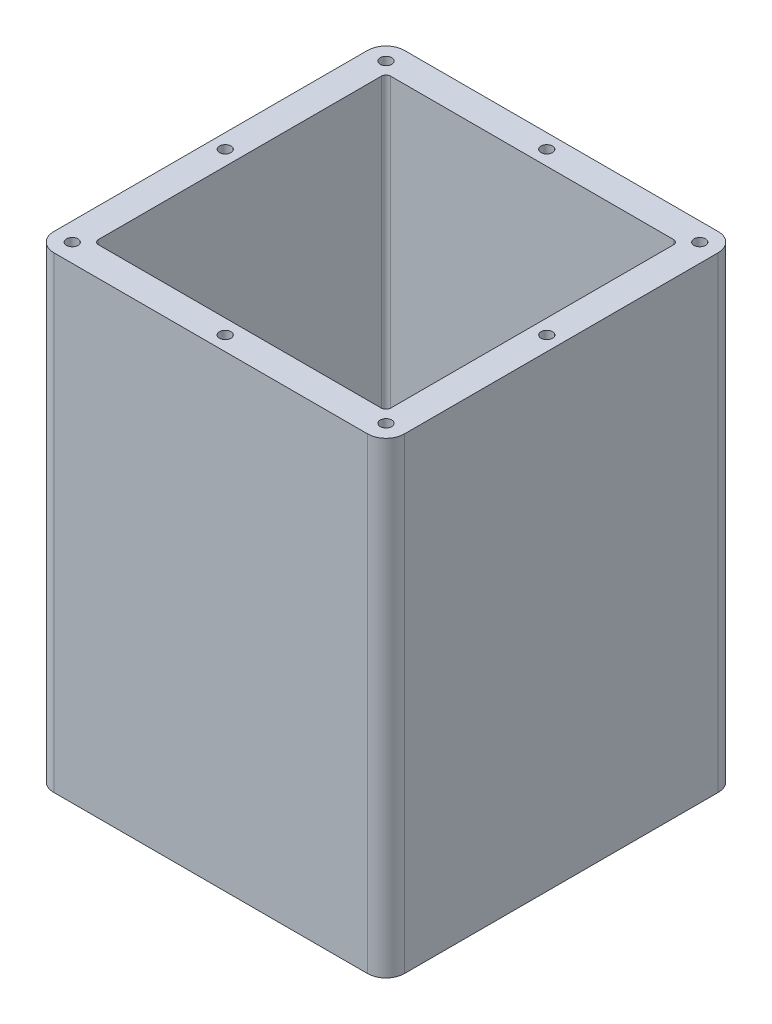
SolidWorks part; units mm, degrees
ref_plane "Front Plane" through (0, 0, 0) normal (0, 0, 1) x (1, 0, 0)
ref_plane "Top Plane" through (0, 0, 0) normal (0, 1, 0) x (1, 0, 0)
ref_plane "Right Plane" through (0, 0, 0) normal (1, 0, 0) x (0, 0, -1)
sketch "Sketch1" plane through (0, 0, 0) normal (0, 1, 0) x (1, 0, 0)
  line L1 (-35.56, -38.1) -> (35.56, -38.1)
  line L2 (-38.1, -35.56) -> (-38.1, 35.56)
  line L3 (-35.56, 38.1) -> (35.56, 38.1)
  line L4 (38.1, -35.56) -> (38.1, 35.56)
  line L5 (-38.1, -38.1) -> (38.1, 38.1) construction
  line L6 (-38.1, 38.1) -> (38.1, -38.1) construction
  arc A0 (-35.56, -38.1) -> (-38.1, -35.56) centre (-35.56, -35.56) cw
  arc A1 (35.56, -38.1) -> (38.1, -35.56) centre (35.56, -35.56) ccw
  arc A2 (35.56, 38.1) -> (38.1, 35.56) centre (35.56, 35.56) cw
  arc A3 (-38.1, 35.56) -> (-35.56, 38.1) centre (-35.56, 35.56) cw
  point P0 (0, 0)
  dimension "D3" = 2.54
  dimension "D1" = 76.2
  dimension "D2" = 76.2
extrude "Boss-Extrude1" add sketch "Sketch1" along normal blind 101.604
sketch "Sketch9" plane through (0, 101.604, 0) normal (0, 1, 0) x (1, 0, 0)
  line L0 (35.56, 38.1) -> (-35.56, 38.1) construction
  line L1 (-30.56, -33.1) -> (30.56, -33.1)
  line L2 (-33.1, -30.56) -> (-33.1, 30.56)
  line L3 (-30.56, 33.1) -> (30.56, 33.1)
  line L4 (33.1, -30.56) -> (33.1, 30.56)
  line L5 (-33.1, -33.1) -> (33.1, 33.1) construction
  line L6 (-33.1, 33.1) -> (33.1, -33.1) construction
  line L7 (38.1, -35.56) -> (38.1, 35.56) construction
  arc A0 (-30.56, -33.1) -> (-33.1, -30.56) centre (-30.56, -30.56) cw
  arc A1 (30.56, -33.1) -> (33.1, -30.56) centre (30.56, -30.56) ccw
  arc A2 (30.56, 33.1) -> (33.1, 30.56) centre (30.56, 30.56) cw
  arc A3 (-33.1, 30.56) -> (-30.56, 33.1) centre (-30.56, 30.56) cw
  point P0 (0, 0)
  dimension "D3" = 2.54
  dimension "D1" = 5
  dimension "D2" = 5
extrude "Cut-Extrude1" cut sketch "Sketch9" against normal blind 246.126
sketch "Sketch13" plane through (0, 0, -33.1) normal (0, 0, 1) x (1, 0, 0)
  line L1 (-20, 36.007) -> (20, 36.007)
  line L2 (-20, 36.007) -> (-20, 76.007)
  line L3 (-20, 76.007) -> (20, 76.007)
  line L4 (20, 36.007) -> (20, 76.007)
  line L5 (-20, 36.007) -> (20, 76.007) construction
  line L6 (-20, 76.007) -> (20, 36.007) construction
  point P0 (0, 56.007)
  dimension "D1" = 40
  dimension "D2" = 40
sketch "Sketch14" plane through (0, 101.604, 0) normal (0, 1, 0) x (1, 0, 0)
  line L2 (-38.1, -38.1) -> (38.1, -38.1)
  line L4 (-38.1, -38.1) -> (-38.1, 38.1)
  line L5 (-31.75, 31.75) -> (31.75, 31.75)
  line L6 (-31.75, 31.75) -> (-31.75, -31.75)
  line L7 (-31.75, -31.75) -> (31.75, -31.75)
  line L8 (31.75, 31.75) -> (31.75, -31.75)
  line L9 (-31.75, 31.75) -> (31.75, -31.75) construction
  line L10 (-31.75, -31.75) -> (31.75, 31.75) construction
  line L11 (-38.1, 38.1) -> (38.1, 38.1)
  line L12 (38.1, -38.1) -> (38.1, 38.1)
  line L13 (-38.1, -38.1) -> (38.1, 38.1) construction
  line L14 (-38.1, 38.1) -> (38.1, -38.1) construction
  point P0 (0, 0)
  point P9 (0, 0)
extrude "Boss-Extrude3" add sketch "Sketch14" against normal blind 101.604
fillet "Fillet1" radius 4 4 edges at (-38.1, 50.802, -38.1) (-38.1, 50.802, 38.1) (38.1, 50.802, 38.1) (38.1, 50.802, -38.1)
sketch "Sketch17" plane through (0, 101.604, 0) normal (0, 1, 0) x (1, 0, 0)
  point P0 (-34.1, 34.1)
  point P3 (34.1, 34.1)
  point P6 (34.1, -34.1)
  point P9 (-34.1, -34.1)
  point P21 (-34.95, 0)
  point P24 (34.95, 0)
  point P27 (0, -34.95)
  point P30 (0, 34.95)
hole_wizard "M3x0.5 Tapped Hole2" positions "Sketch17" profile "Sketch18" tap size "M3x0.5" standard "ANSI Metric"
sketch "Sketch18" plane through (-34.1, 101.604, -34.1) normal (1, 0, 0) x (0, 0, 1)
  line L0 (0, 0) -> (0, 8.2511)
  line L1 (0, 8.2511) -> (1.25, 7.5)
  line L2 (1.25, 7.5) -> (1.25, 0)
  line L5 (1.25, 0) -> (0, 0)
  line L10 (0, 8.2511) -> (-1.25, 7.5) construction
  line L11 (0, -6.35) -> (0, 107.95) construction
  dimension "Tap Drill Dia." = 2.5
  dimension "Tap Drill Depth" = 7.5
  dimension "Drill Angle" = 118
sketch "Sketch21" plane through (38.1, 0, 0) normal (1, 0, 0) x (0, 0, -1)
  circle A0 centre (0, 76.708) radius 10
  circle A1 centre (0, 33.7027) radius 10
  dimension "D2" = 20
  dimension "D3" = 20
sketch "Sketch24" plane through (0, 0, 0) normal (0, -1, 0) x (-1, 0, 0)
  point P0 (-34.1, 34.1)
  point P2 (34.1, 34.1)
  point P4 (34.1, -34.1)
  point P6 (-34.1, -34.1)
  point P16 (-34.95, 0)
  point P19 (0, 34.95)
  point P22 (34.95, 0)
  point P25 (0, -34.95)
hole_wizard "M3x0.5 Tapped Hole1" positions "Sketch24" profile "Sketch23" tap size "M3x0.5" standard "ANSI Metric"
sketch "Sketch23" plane through (34.1, 0, -34.1) normal (1, 0, 0) x (0, 0, -1)
  line L0 (0, 0) -> (0, 8.2511)
  line L1 (0, 8.2511) -> (1.25, 7.5)
  line L2 (1.25, 7.5) -> (1.25, 0)
  line L5 (1.25, 0) -> (0, 0)
  line L10 (0, 8.2511) -> (-1.25, 7.5) construction
  line L11 (0, -6.35) -> (0, 107.95) construction
  dimension "Tap Drill Dia." = 2.5
  dimension "Tap Drill Depth" = 7.5
  dimension "Drill Angle" = 118
fillet "Fillet2" radius 1 4 edges at (31.75, 50.802, 31.75) (-31.75, 50.802, 31.75) (-31.75, 50.802, -31.75) (31.75, 50.802, -31.75)
